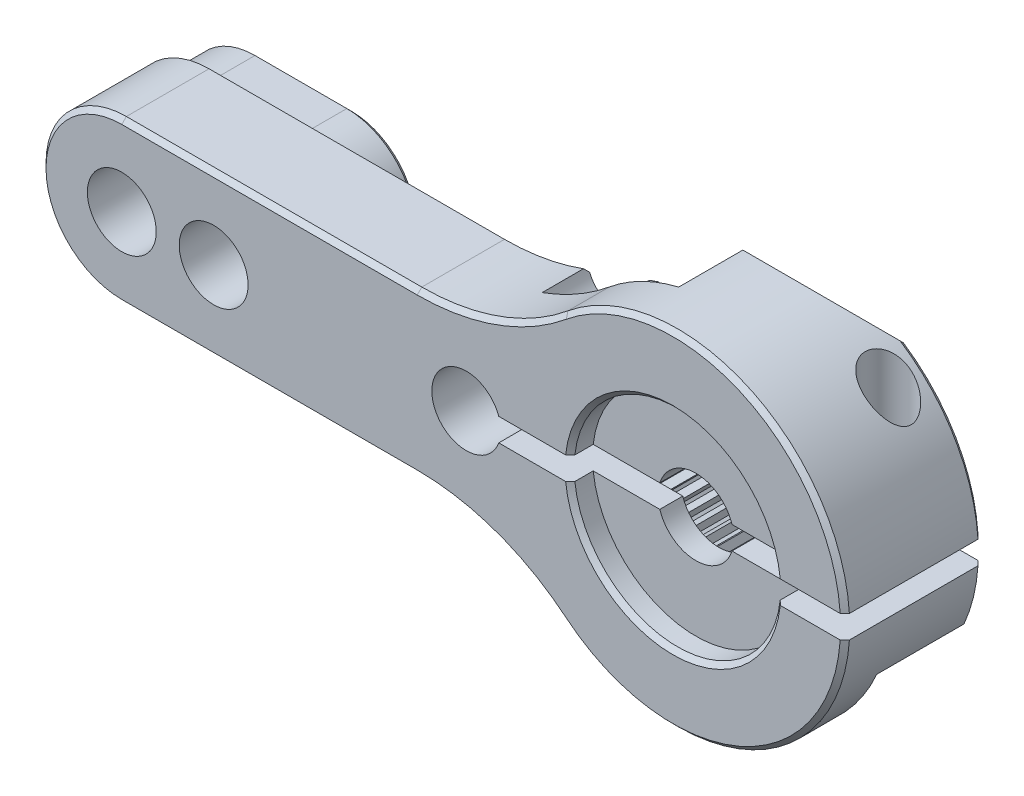
SolidWorks part; units mm, degrees
material "1060 Alloy"
ref_plane "Plan de face" through (0, 0, 0) normal (0, 0, 1) x (1, 0, 0)
ref_plane "Plan de dessus" through (0, 0, 0) normal (0, 1, 0) x (1, 0, 0)
ref_plane "Plan de droite" through (0, 0, 0) normal (1, 0, 0) x (0, 0, -1)
sketch "Esquisse1" plane through (0, 0, 0) normal (0, 0, 1) x (1, 0, 0)
  line L0 (-11.1355, 3.5) -> (-24, 3.5)
  line L1 (-24, -3.5) -> (-11.1355, -3.5)
  line L2 (0, 0) -> (-40.4273, 0) construction
  line L3 (-27.5, 8.0474) -> (-27.5, -5.9021) construction
  line L4 (7.5, 11.0169) -> (7.5, -8.8025) construction
  circle A1 centre (0, 0) radius 1.65
  arc A2 (-4.7724, 5.7857) -> (-4.7724, -5.7857) centre (0, 0) cw
  arc A3 (-24, 3.5) -> (-24, -3.5) centre (-24, 0) ccw
  arc A4 (-11.1355, -3.5) -> (-4.7724, -5.7857) centre (-11.1355, -13.5) cw
  arc A5 (-4.7724, 5.7857) -> (-11.1355, 3.5) centre (-11.1355, 13.5) cw
  circle A6 centre (-9, 0) radius 1.5
  circle A7 centre (-24, 0) radius 1.5
  circle A8 centre (-20, 0) radius 1.5
  point P14 (-6.6332, -3.5)
  point P18 (-6.6332, 3.5)
  dimension "D1" = 7.5
  dimension "D2" = 3.3
  dimension "D5" = 10
  dimension "D6" = 3
  dimension "D7" = 3
  dimension "D8" = 3
  dimension "D3" = 7
  dimension "D4" = 35
  dimension "D9" = 9
  dimension "D10" = 11
  dimension "D11" = 4
extrude "Boss.-Extru.1" add sketch "Esquisse1" along normal blind 6
sketch "Esquisse2" plane through (0, 0, 6) normal (0, 0, 1) x (1, 0, 0)
  line L0 (7.5, 0) -> (-41.9387, 0) construction
  line L1 (8.5, 0.5) -> (-10.4142, 0.5)
  line L2 (8.5, 0.5) -> (8.5, -0.5)
  line L3 (8.5, -0.5) -> (-10.4142, -0.5)
  line L4 (-10.4142, 0.5) -> (-10.4142, -0.5)
  arc A0 (-4.7724, -5.7857) -> (-4.7724, 5.7857) centre (0, 0) ccw construction
  circle A1 centre (-9, 0) radius 1.5 construction
  dimension "D1" = 1
  dimension "D2" = 1
extrude "Enlèv. mat.-Extru.1" cut sketch "Esquisse2" against normal blind 6
sketch "Esquisse3" plane through (0, 0, 0) normal (0, 0, -1) x (-1, 0, 0)
  line L2 (24, -3.5) -> (11.1355, -3.5)
  line L3 (24, -3.5) -> (11.1355, -3.5)
  line L5 (24, 0) -> (20, 0) construction
  line L6 (11.1355, 3.5) -> (24, 3.5)
  line L7 (11.1355, 3.5) -> (24, 3.5)
  line L8 (24, -3) -> (20, -3)
  line L9 (24, 3) -> (20, 3)
  arc A0 (4.7724, 5.7857) -> (4.7724, -5.7857) centre (0, 0) cw
  arc A5 (11.1355, -3.5) -> (4.7724, -5.7857) centre (11.1355, -13.5) ccw
  arc A6 (11.1355, -3.5) -> (4.7724, -5.7857) centre (11.1355, -13.5) ccw
  arc A10 (24, -3) -> (24, 3) centre (24, 0) ccw
  arc A11 (20, 3) -> (20, -3) centre (20, 0) ccw
  arc A12 (24, -3.5) -> (24, 3.5) centre (24, 0) ccw
  arc A13 (4.7724, 5.7857) -> (11.1355, 3.5) centre (11.1355, 13.5) ccw
  arc A14 (24, -3.5) -> (24, 3.5) centre (24, 0) ccw
  arc A15 (4.7724, 5.7857) -> (11.1355, 3.5) centre (11.1355, 13.5) ccw
  point P5 (22, 0)
  dimension "D3" = 4
  dimension "D4" = 0.5
  dimension "D1" = 0
  dimension "D2" = 0
extrude "Enlèv. mat.-Extru.2" cut sketch "Esquisse3" against normal blind 2
sketch "Esquisse4" plane through (0, 0, 0) normal (0, 0, -1) x (-1, 0, 0)
  line L0 (-7.5, -3) -> (-3.25, -3)
  line L1 (-1.75, -4.5) -> (-1.75, -7.5)
  line L2 (-1.75, -7.5) -> (-7.5, -7.5)
  line L3 (-7.5, -7.5) -> (-7.5, -3)
  line L4 (-1.5724, -0.5) -> (-7.4833, -0.5) construction
  line L5 (1.5724, 0.5) -> (7.4833, 0.5) construction
  line L6 (1.75, 7.5) -> (7.75, 7.5)
  line L7 (1.75, 7.5) -> (1.75, 4.5)
  line L8 (3.25, 3) -> (6.25, 3)
  line L9 (7.75, 7.5) -> (7.75, 4.5)
  arc A0 (7.4833, 0.5) -> (-7.4833, 0.5) centre (0, 0) ccw construction
  arc A1 (-7.4833, -0.5) -> (7.4833, -0.5) centre (0, 0) ccw construction
  arc A2 (-3.25, -3) -> (-1.75, -4.5) centre (-3.25, -4.5) cw
  arc A3 (6.25, 3) -> (7.75, 4.5) centre (6.25, 4.5) ccw
  arc A4 (1.75, 4.5) -> (3.25, 3) centre (3.25, 4.5) ccw
  point P14 (-1.75, -3)
  dimension "D3" = 1.5
  dimension "D7" = 1.5
  dimension "D1" = 5.75
  dimension "D2" = 2.5
  dimension "D4" = 3.5
  dimension "D5" = 2.5
  dimension "D6" = 6
extrude "Enlèv. mat.-Extru.3" cut sketch "Esquisse4" against normal blind 4
sketch "Esquisse5" plane through (0, -3, 0) normal (0, -1, 0) x (1, 0, 0)
  line L0 (3.25, 4) -> (6.8739, 4) construction
  line L2 (6.8739, 4) -> (6.8739, 0) construction
  circle A0 centre (4.8739, 1.5) radius 1
  dimension "D1" = 2
  dimension "D2" = 2.5
  dimension "D3" = 2
extrude "Enlèv. mat.-Extru.4" cut sketch "Esquisse5" against normal through all
sketch "Esquisse6" plane through (0, 3, 0) normal (0, 1, 0) x (1, 0, 0)
  line L0 (-7.4833, -2) -> (-7.4833, 0) construction
  line L1 (4.8739, -1.5) -> (-10.9129, -1.5) construction
  circle A0 centre (-5.2333, -1.5) radius 1
  dimension "D1" = 2
  dimension "D2" = 2.25
extrude "Enlèv. mat.-Extru.5" cut sketch "Esquisse6" against normal through all
sketch "Esquisse7" plane through (0, 0, 0) normal (1, 0, 0) x (0, 0, -1)
  line L0 (-1.4142, 7.5) -> (0, 6.0858)
  line L1 (0, 7.5) -> (-6, 7.5) construction
  line L2 (0, 0.5) -> (0, 7.5) construction
  line L3 (0, 6.0858) -> (0, 7.5)
  line L4 (0, 7.5) -> (-1.4142, 7.5)
  line L5 (0, -6.0858) -> (-1.4142, -7.5)
  line L6 (0, -7.293) -> (0, -4.5) construction
  line L7 (-1.4142, -7.5) -> (0, -7.5)
  line L8 (0, -7.5) -> (0, -6.0858)
  line L9 (0, -7.5) -> (0, -0.5) construction
  dimension "D1" = 2
  dimension "D2" = 45
  dimension "D3" = 45
  dimension "D4" = 2
  dimension "D5" = 15
extrude "Enlèv. mat.-Extru.6" cut sketch "Esquisse7" against normal blind 10 and the other way blind 10
sketch "Esquisse8" plane through (0, 0, 0) normal (0, 0, -1) x (-1, 0, 0)
  circle A0 centre (0, 0) radius 3
  dimension "D1" = 6
extrude "Enlèv. mat.-Extru.7" cut sketch "Esquisse8" against normal blind 4
sketch "Esquisse9" plane through (0, 0, 0) normal (0, 0, -1) x (-1, 0, 0)
  line L0 (0, 0) -> (0, 3.5855) construction
  line L1 (-0.8887, 3) -> (1.1976, 3) construction
  line L2 (-0.2021, 3) -> (0, 2.65)
  line L3 (0, 2.65) -> (0.2021, 3)
  line L4 (0.2021, 3) -> (-0.2021, 3)
  arc A0 (2.958, 0.5) -> (-2.958, 0.5) centre (0, 0) ccw construction
  dimension "D1" = 30
  dimension "D2" = 0.35
extrude "Boss.-Extru.2" add sketch "Esquisse9" against normal up to surface (4 mm away) up to face at (0, 1.4125, 4)
pattern_circular "Répétition circulaire1" count 36 over 360 about axis through (0, 0, 4) along (0, 0, -1) skipping 9, 27 of "Boss.-Extru.2"
sketch "Esquisse10" plane through (0, 0, 0) normal (0, 0, -1) x (-1, 0, 0)
  line L0 (7.4833, -0.5) -> (2.9581, -0.5) construction
  line L1 (-7.4833, 0.5) -> (3.8917, 0.5)
  line L2 (-7.4833, 0.5) -> (-7.4833, -0.5)
  line L3 (-7.4833, -0.5) -> (3.8917, -0.5)
  line L4 (3.8917, 0.5) -> (3.8917, -0.5)
extrude "Enlèv. mat.-Extru.8" cut sketch "Esquisse10" against normal through all
chamfer "Chanfrein1" distance 0.2 angle 45 20 edges at (2.9702, 6.8868, 6) (-7.7549, 4.0888, 6) (-17.5678, 3.5, 6) (-27.5, 0, 6) (-17.5678, -3.5, 6) (2.9702, -6.8868, 6) (-7.7549, -4.0888, 6) (-22, 3, 0) (-17, 0, 0) (-27, 0, 0) (-22, -3, 0) (-9.3901, 3.6535, 2) (-17.5678, 3.5, 2) (-27.5, 0, 2) (-17.5678, -3.5, 2) (-8.5271, -3.8462, 2) (7.2866, -1.7763, 0) (6.5578, 3.6395, 0) (-7.2716, 1.8368, 0) (-6.5578, -3.6395, 0)
sketch "Esquisse11" plane through (0, 0, 6) normal (0, 0, 1) x (1, 0, 0)
  circle A0 centre (0, 0) radius 4.5
  dimension "D1" = 9
extrude "Enlèv. mat.-Extru.9" cut sketch "Esquisse11" against normal blind 1
chamfer "Chanfrein2" distance 0.2 angle 45 2 edges at (0, -4.5, 6) (0, 4.5, 6)
sketch "Sketch1" plane through (0, 0, 6) normal (0, 0, 1) x (1, 0, 0)
  line L0 (-11.1355, -3.5) -> (-24, -3.5) construction
  line L1 (-24, 3.5) -> (-11.1355, 3.5) construction
  line L2 (-11.1355, -3.5) -> (-24, -3.5)
  line L3 (-24, 3.5) -> (-11.1355, 3.5)
  line L4 (-11.1355, -3.7) -> (-24, -3.7)
  line L5 (-24, 3.7) -> (-11.1355, 3.7)
  arc A0 (-24, 3.5) -> (-24, -3.5) centre (-24, 0) ccw construction
  arc A1 (-24, 3.5) -> (-24, -3.5) centre (-24, 0) ccw
  arc A2 (-4.7724, -5.7857) -> (-11.1355, -3.5) centre (-11.1355, -13.5) ccw construction
  arc A3 (-4.7724, -5.7857) -> (7.4833, -0.5) centre (0, 0) ccw construction
  arc A4 (7.4833, 0.5) -> (-4.7724, 5.7857) centre (0, 0) ccw construction
  arc A5 (-11.1355, 3.5) -> (-4.7724, 5.7857) centre (-11.1355, 13.5) ccw construction
  arc A6 (-4.7724, -5.7857) -> (-11.1355, -3.5) centre (-11.1355, -13.5) ccw
  arc A7 (-4.7724, -5.7857) -> (7.4833, -0.5) centre (0, 0) ccw
  arc A8 (7.4833, 0.5) -> (-4.7724, 5.7857) centre (0, 0) ccw
  arc A9 (-11.1355, 3.5) -> (-4.7724, 5.7857) centre (-11.1355, 13.5) ccw
  arc A10 (7.4833, 0.5) -> (7.4833, -0.5) centre (0, 0) cw
  circle A11 centre (-9, 0) radius 20
  arc A12 (-24, 3.7) -> (-24, -3.7) centre (-24, 0) ccw
  arc A13 (-11.1355, 3.7) -> (-4.8996, 5.94) centre (-11.1355, 13.5) ccw
  arc A14 (7.6829, 0.5133) -> (-4.8996, 5.94) centre (0, 0) ccw
  arc A15 (7.6829, 0.5133) -> (7.6829, -0.5133) centre (0, 0) cw
  arc A16 (-4.8996, -5.94) -> (7.6829, -0.5133) centre (0, 0) ccw
  arc A17 (-4.8996, -5.94) -> (-11.1355, -3.7) centre (-11.1355, -13.5) ccw
  line M1 (7.2829, -0.5) -> (4.6733, -0.5)
  arc M2 (4.6733, -0.5) -> (-4.6733, -0.5) centre (0, 0) cw
  line M3 (-4.6733, -0.5) -> (-7.5858, -0.5)
  arc M4 (-7.5858, -0.5) -> (-7.5858, 0.5) centre (-9, 0) cw
  line M5 (-7.5858, 0.5) -> (-4.6733, 0.5)
  arc M6 (-4.6733, 0.5) -> (4.6733, 0.5) centre (0, 0) cw
  line M7 (4.6733, 0.5) -> (7.2829, 0.5)
  arc M8 (7.2829, 0.5) -> (-4.6451, 5.6314) centre (0, 0) ccw
  arc M9 (-4.6451, 5.6314) -> (-11.1355, 3.3) centre (-11.1355, 13.5) cw
  line M10 (-11.1355, 3.3) -> (-24, 3.3)
  arc M11 (-24, 3.3) -> (-24, -3.3) centre (-24, 0) ccw
  line M12 (-24, -3.3) -> (-11.1355, -3.3)
  arc M13 (-11.1355, -3.3) -> (-4.6451, -5.6314) centre (-11.1355, -13.5) cw
  arc M14 (-4.6451, -5.6314) -> (7.2829, -0.5) centre (0, 0) ccw
  circle M15 centre (-24, 0) radius 1.5
  circle M16 centre (-20, 0) radius 1.5
  dimension "D1" = 40
  dimension "D2" = 0.2
extrude "Boss-Extrude1" add sketch "Sketch1" along normal blind 10 from offset 5 separate body contours A11 A16 A17 L4 A12 L5 A13 A14 A15 region at (-28.4343, 0, 6)
extrude "Boss-Extrude2" add sketch "Sketch1<3>" against normal blind 3.5 from offset 15 contours A17 A16 A15 A14 A13 L5 A12 L4 A8 A10 A7 A6 L2 A1 L3 A9 | M14 M1 M2 M3 M4 M5 M6 M7 M8 M9 M10 M11 M12 M13 M15 M16 | A10 A8 A9 L3 A1 L2 A6 A7 M1 M14 M13 M12 M11 M10 M9 M8 M7 M6 M5 M4 M3 M2 region at (-2.1938, 0, 6) region at (-17.5678, -3.6614, 6) region at (2.7365, -6.361, 6)
sketch "Sketch1<3>" plane through (0, 0, 6) normal (0, 0, 1) x (1, 0, 0) same geometry as "Sketch1"
sketch "Sketch3" plane through (0, 0, 21) normal (0, 0, 1) x (1, 0, 0)
  circle A0 centre (0, 0) radius 1.65
  circle A1 centre (-9, 0) radius 1.65
  dimension "D1" = 3.3
  dimension "D2" = 3.3
extrude "Cut-Extrude1" cut sketch "Sketch3" against normal up to surface (3.5 mm away) up to face at (-11.7968, 0, 17.5)
delete or keep bodies "Body-Delete/Keep 1" type delete bodies bodies 116
